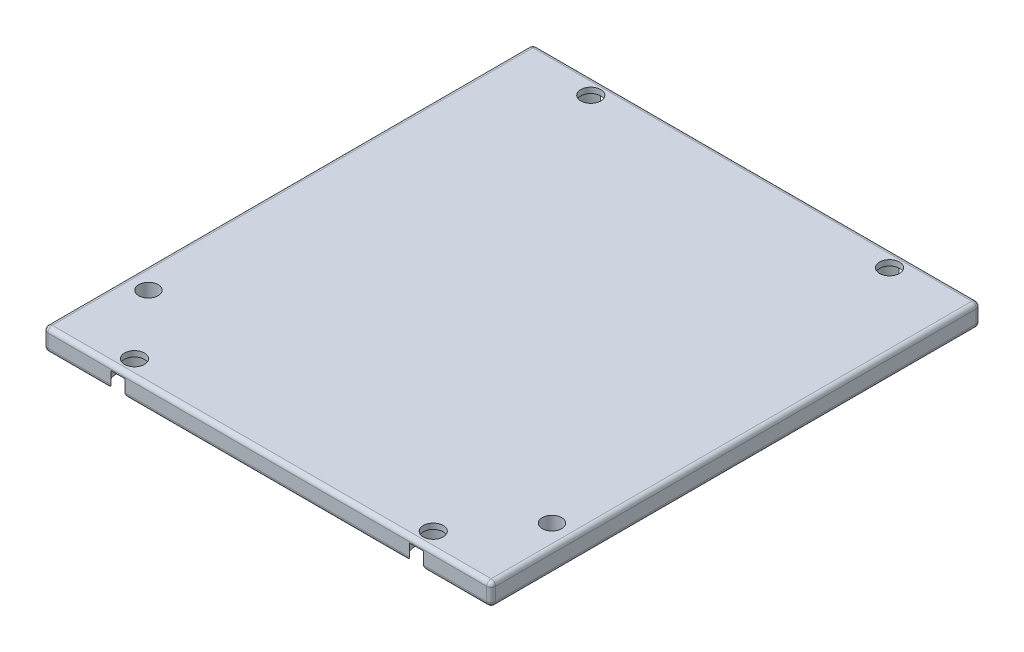
SolidWorks part; units mm, degrees
ref_plane "Front Plane" through (0, 0, 0) normal (0, 0, 1) x (1, 0, 0)
ref_plane "Top Plane" through (0, 0, 0) normal (0, 1, 0) x (1, 0, 0)
ref_plane "Right Plane" through (0, 0, 0) normal (1, 0, 0) x (0, 0, -1)
sketch "Sketch1" plane through (0, 0, 0) normal (0, 1, 0) x (1, 0, 0)
  line L0 (40.5, 88.55) -> (40.5, 0) construction
  line L1 (0, 0) -> (81, 0)
  line L2 (0, 0) -> (0, 88.55)
  line L3 (0, 88.55) -> (81, 88.55)
  line L4 (81, 0) -> (81, 88.55)
  circle A0 centre (4, 15) radius 1.75
  circle A1 centre (13.475, 3) radius 1.65
  circle A2 centre (13.475, 85.55) radius 1.65
  circle A3 centre (77, 15) radius 1.75
  circle A4 centre (67.525, 3) radius 1.65
  circle A5 centre (67.525, 85.55) radius 1.65
  point P12 (4, 15)
  dimension "D3" = 4
  dimension "D4" = 13.475
  dimension "D5" = 3
  dimension "D6" = 3
  dimension "D7" = 15
  dimension "D8" = 3.3
  dimension "D9" = 3.3
  dimension "D10" = 3.5
  dimension "D11" = 13.475
  dimension "D1" = 81
  dimension "D2" = 88.55
extrude "Boss-Extrude1" add sketch "Sketch1" along normal blind 4
fillet "Fillet3" radius 0.8 12 edges at (0, 2, -88.55) (0, 4, -44.275) (0, 0, -44.275) (0, 2, 0) (40.5, 4, 0) (40.5, 0, 0) (81, 2, 0) (81, 4, -44.275) (81, 0, -44.275) (81, 2, -88.55) (40.5, 4, -88.55) (40.5, 0, -88.55)
sketch "Sketch2" plane through (0, 0, 0) normal (0, -1, 0) x (1, 0, 0)
  line L1 (10.75, -25.5) -> (15.75, -25.5)
  line L2 (10.75, -25.5) -> (10.75, -45.5)
  line L3 (10.75, -45.5) -> (15.75, -45.5)
  line L4 (15.75, -25.5) -> (15.75, -45.5)
  circle A1 centre (4, -15) radius 1.75 construction
  dimension "D3" = 10.5
  dimension "D1" = 6.75
  dimension "D2" = 20
  dimension "D4" = 5
extrude "Boss-Extrude2" add sketch "Sketch2" along normal blind 8.8
sketch "Sketch5" plane through (0, 0, -45.5) normal (0, 0, -1) x (-1, 0, 0)
  line L0 (-15.75, -8.8) -> (-15.75, 0) construction
  line L1 (-10.75, 0) -> (-13.95, 0)
  line L2 (-10.75, 0) -> (-10.75, -6.8)
  line L3 (-10.75, -6.8) -> (-13.95, -6.8)
  line L4 (-13.95, 0) -> (-13.95, -6.8)
  dimension "D1" = 6.8
  dimension "D2" = 1.8
extrude "Cut-Extrude1" cut sketch "Sketch5" against normal through all
fillet "Fillet1" radius 3 1 edges at (15.75, 0, -35.5) second distance 5 first distance on face at (13.475, 0, -1.35)
fillet "Fillet2" radius 0.5 9 edges at (13.25, -8.8, -25.5) (13.25, -8.8, -45.5) (10.75, -7.8, -25.5) (10.75, -7.8, -45.5) (10.75, -6.8, -35.5) (13.95, -3.4, -45.5) (13.95, -3.4, -25.5) (10.75, -8.8, -35.5) (15.75, -8.8, -35.5)
ref_axis "Axis1" through (40.5, 0, -0.8) along (0, 0, -1)
ref_plane "Plane1" through (40.5, 0, 0) normal (-1, 0, 0) x (0, 0, -1)
mirror "Mirror1" about plane through (40.5, 0, 0) normal (-1, 0, 0) of "Fillet2", "Fillet1", "Cut-Extrude1", "Boss-Extrude2"
sketch "Sketch7" plane through (0, 0, 0) normal (0, -1, 0) x (1, 0, 0)
  point P0 (13.475, -3)
  point P1 (13.475, -85.55)
  point P3 (67.525, -85.55)
  point P5 (67.525, -3)
hole_wizard "CBORE for M3 SHCS1" positions "Sketch7" profile "Sketch12" counterbore size "M3" standard "ANSI Metric" end condition through all
sketch "Sketch12" plane through (13.475, 0, -3) normal (1, 0, 0) x (0, 0, -1)
  line L0 (0, 0) -> (0, 4)
  line L1 (0, 4) -> (1.8, 4)
  line L3 (1.8, 4) -> (1.8, 3)
  line L4 (1.8, 3) -> (3.25, 3)
  line L5 (3.25, 3) -> (3.25, 0)
  line L7 (3.25, 0) -> (0, 0)
  line L11 (0, -6.35) -> (0, 107.95) construction
  dimension "Thru Hole Dia." = 3.6
  dimension "Thru Hole Depth" = 4
  dimension "C'Bore Dia." = 6.5
  dimension "C'Bore Depth" = 3
